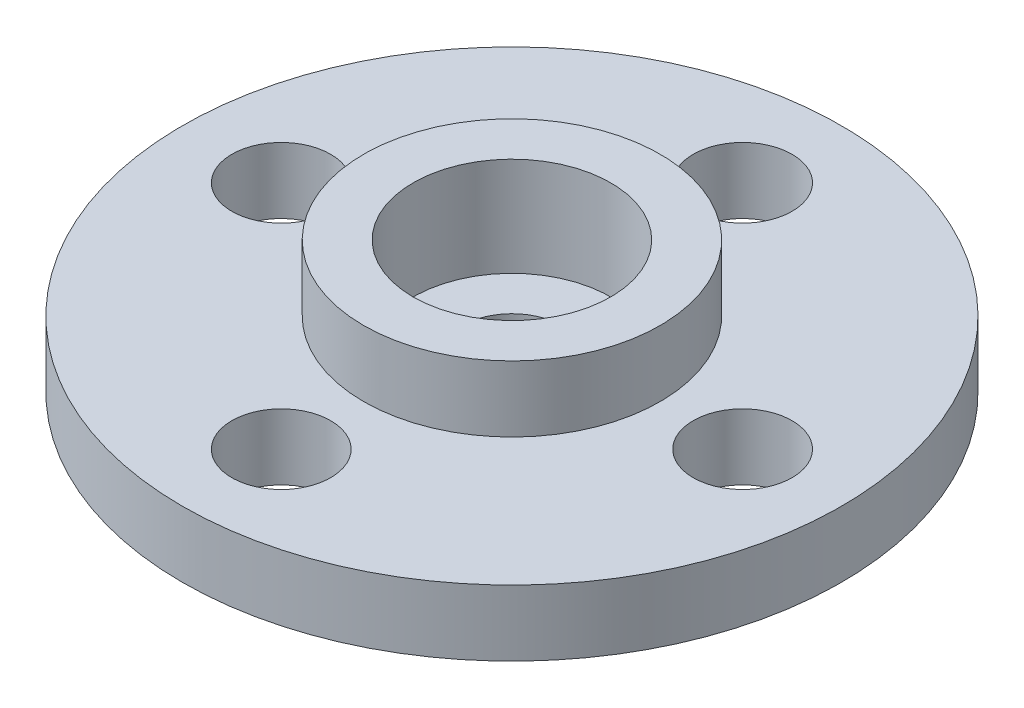
SolidWorks part; units mm, degrees
ref_plane "Спереди" through (0, 0, 0) normal (0, 0, 1) x (1, 0, 0)
ref_plane "Сверху" through (0, 0, 0) normal (0, 1, 0) x (1, 0, 0)
ref_plane "Справа" through (0, 0, 0) normal (1, 0, 0) x (0, 0, -1)
sketch "Эскиз1" plane through (0, 0, 0) normal (0, 1, 0) x (1, 0, 0)
  circle A0 centre (0, 0) radius 10
  dimension "D1" = 20
extrude "тело" add sketch "Эскиз1" along normal blind 2
sketch "Эскиз2" plane through (0, 2, 0) normal (0, 1, 0) x (1, 0, 0)
  circle A0 centre (0, 0) radius 4.5
  dimension "D1" = 9
extrude "выступ крепления к оси" add sketch "Эскиз2" along normal blind 2
sketch "Эскиз3" plane through (0, 4, 0) normal (0, 1, 0) x (1, 0, 0)
  circle A0 centre (0, 0) radius 3
  dimension "D1" = 6
extrude "ось сервы" cut sketch "Эскиз3" against normal blind 3
sketch "Эскиз4" plane through (0, 1, 0) normal (0, 1, 0) x (1, 0, 0)
  circle A0 centre (0, 0) radius 1.5
  dimension "D1" = 3
extrude "отверстие в оси" cut sketch "Эскиз4" against normal through all
sketch "Эскиз5" plane through (0, 2, 0) normal (0, 1, 0) x (1, 0, 0)
  circle A0 centre (0, 0) radius 7 construction
  circle A1 centre (7, 0) radius 1.5
  dimension "D1" = 14
  dimension "D2" = 3
extrude "крепление к детали" cut sketch "Эскиз5" against normal through all
pattern_circular "Круговой массив1" count 4 every 90 about axis through (0, 1, 0) along (0, 1, 0) of "крепление к детали"
